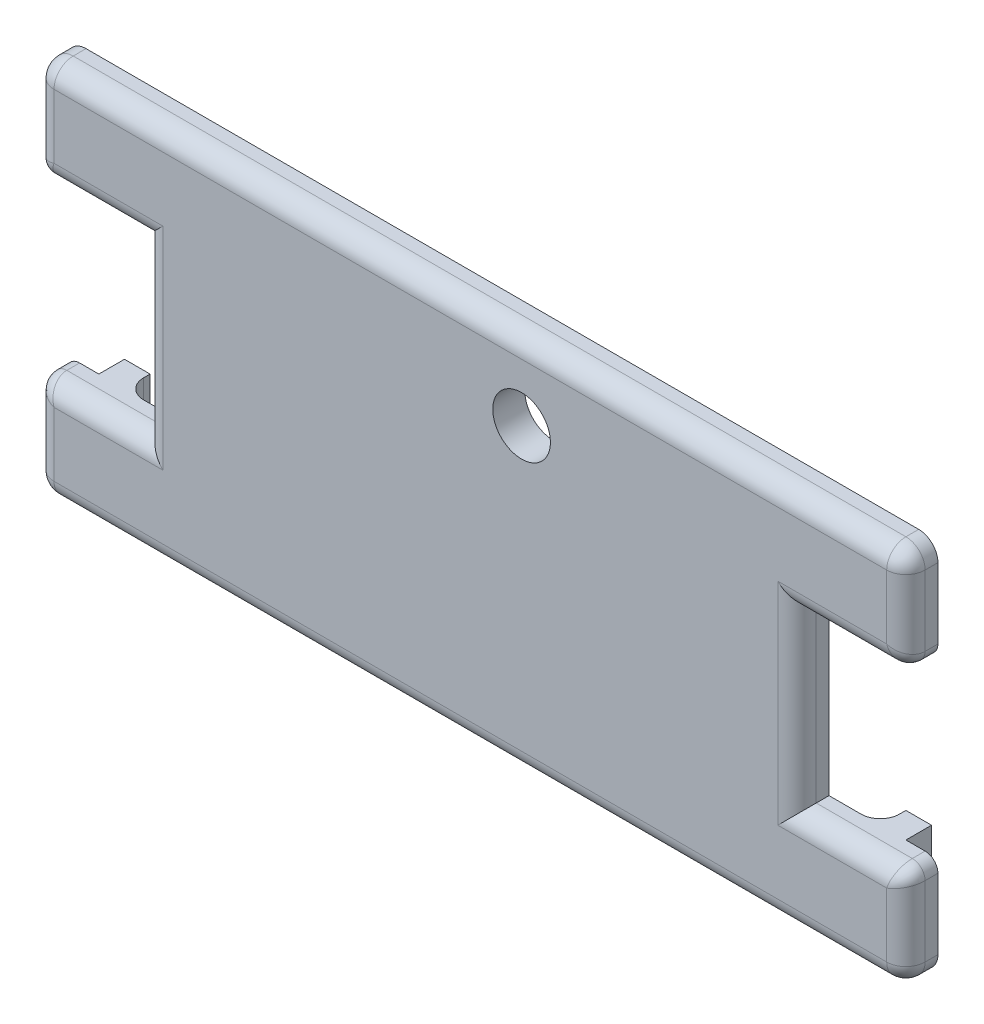
SolidWorks part; units mm, degrees
ref_plane "Front Plane" through (0, 0, 0) normal (0, 0, 1) x (1, 0, 0)
ref_plane "Top Plane" through (0, 0, 0) normal (0, 1, 0) x (1, 0, 0)
ref_plane "Right Plane" through (0, 0, 0) normal (1, 0, 0) x (0, 0, -1)
sketch "Sketch1" plane through (0, 0, 0) normal (0, 0, 1) x (1, 0, 0)
  line L16 (-34, 13.25) -> (-34, 7.75)
  line L17 (-33, 6.75) -> (-31.5, 6.75)
  line L18 (-31.5, 6.75) -> (-31.5, 10.75)
  line L19 (-30, 12.25) -> (30, 12.25)
  line L20 (31.5, 10.75) -> (31.5, 6.75)
  line L21 (31.5, 6.75) -> (33, 6.75)
  line L22 (34, 7.75) -> (34, 13.25)
  line L23 (32.5, 14.75) -> (-32.5, 14.75)
  line L24 (-34, 13.25) -> (-34, 7.75)
  line L25 (-33, 6.75) -> (-31.5, 6.75)
  line L26 (-31.5, 6.75) -> (-31.5, 10.75)
  line L27 (-30, 12.25) -> (30, 12.25)
  line L28 (31.5, 10.75) -> (31.5, 6.75)
  line L29 (31.5, 6.75) -> (33, 6.75)
  line L30 (34, 7.75) -> (34, 13.25)
  line L31 (32.5, 14.75) -> (-32.5, 14.75)
  line L40 (-31.5, -6.75) -> (-33, -6.75)
  line L41 (-34, -7.75) -> (-34, -13.25)
  line L42 (-32.5, -14.75) -> (32.5, -14.75)
  line L43 (34, -13.25) -> (34, -7.75)
  line L44 (33, -6.75) -> (31.5, -6.75)
  line L45 (31.5, -6.75) -> (31.5, -10.75)
  line L46 (30, -12.25) -> (-30, -12.25)
  line L47 (-31.5, -10.75) -> (-31.5, -6.75)
  line L48 (-31.5, -6.75) -> (-33, -6.75)
  line L49 (-34, -7.75) -> (-34, -13.25)
  line L50 (-32.5, -14.75) -> (32.5, -14.75)
  line L51 (34, -13.25) -> (34, -7.75)
  line L52 (33, -6.75) -> (31.5, -6.75)
  line L53 (31.5, -6.75) -> (31.5, -10.75)
  line L54 (30, -12.25) -> (-30, -12.25)
  line L55 (-31.5, -10.75) -> (-31.5, -6.75)
  line L64 (-36, 13.25) -> (-36, 7.75)
  line L65 (-33, 4.75) -> (-29.5, 4.75)
  line L66 (-29.5, 4.75) -> (-29.5, 10.25)
  line L67 (-29.5, 10.25) -> (29.5, 10.25)
  line L68 (29.5, 10.25) -> (29.5, 4.75)
  line L69 (29.5, 4.75) -> (33, 4.75)
  line L70 (36, 7.75) -> (36, 13.25)
  line L71 (32.5, 16.75) -> (-32.5, 16.75)
  line L72 (-36, 13.25) -> (-36, 7.75)
  line L73 (-33, 4.75) -> (-29.5, 4.75)
  line L74 (-29.5, 4.75) -> (-29.5, 10.25)
  line L75 (-29.5, 10.25) -> (29.5, 10.25)
  line L76 (29.5, 10.25) -> (29.5, 4.75)
  line L77 (29.5, 4.75) -> (33, 4.75)
  line L78 (36, 7.75) -> (36, 13.25)
  line L79 (32.5, 16.75) -> (-32.5, 16.75)
  line L80 (-31.5, 6.75) -> (-29.5, 6.75)
  line L81 (31.5, 6.75) -> (29.5, 6.75)
  line L82 (31.5, -6.75) -> (-31.5, -6.75)
  line L88 (-29.5, -4.75) -> (-33, -4.75)
  line L89 (-36, -7.75) -> (-36, -13.25)
  line L90 (-32.5, -16.75) -> (32.5, -16.75)
  line L91 (36, -13.25) -> (36, -7.75)
  line L92 (33, -4.75) -> (29.5, -4.75)
  line L93 (29.5, -4.75) -> (29.5, -10.25)
  line L94 (29.5, -10.25) -> (-29.5, -10.25)
  line L95 (-29.5, -10.25) -> (-29.5, -4.75)
  line L96 (-29.5, -4.75) -> (-33, -4.75)
  line L97 (-36, -7.75) -> (-36, -13.25)
  line L98 (-32.5, -16.75) -> (32.5, -16.75)
  line L99 (36, -13.25) -> (36, -7.75)
  line L100 (33, -4.75) -> (29.5, -4.75)
  line L101 (29.5, -4.75) -> (29.5, -10.25)
  line L102 (29.5, -10.25) -> (-29.5, -10.25)
  line L103 (-29.5, -10.25) -> (-29.5, -4.75)
  arc A12 (-34, 7.75) -> (-33, 6.75) centre (-33, 7.75) ccw
  arc A13 (-30, 12.25) -> (-31.5, 10.75) centre (-30, 10.75) ccw
  arc A14 (31.5, 10.75) -> (30, 12.25) centre (30, 10.75) ccw
  arc A15 (33, 6.75) -> (34, 7.75) centre (33, 7.75) ccw
  arc A16 (34, 13.25) -> (32.5, 14.75) centre (32.5, 13.25) ccw
  arc A17 (-32.5, 14.75) -> (-34, 13.25) centre (-32.5, 13.25) ccw
  arc A18 (-34, 7.75) -> (-33, 6.75) centre (-33, 7.75) ccw
  arc A19 (-30, 12.25) -> (-31.5, 10.75) centre (-30, 10.75) ccw
  arc A20 (31.5, 10.75) -> (30, 12.25) centre (30, 10.75) ccw
  arc A21 (33, 6.75) -> (34, 7.75) centre (33, 7.75) ccw
  arc A22 (34, 13.25) -> (32.5, 14.75) centre (32.5, 13.25) ccw
  arc A23 (-32.5, 14.75) -> (-34, 13.25) centre (-32.5, 13.25) ccw
  arc A30 (-33, -6.75) -> (-34, -7.75) centre (-33, -7.75) ccw
  arc A31 (-34, -13.25) -> (-32.5, -14.75) centre (-32.5, -13.25) ccw
  arc A32 (32.5, -14.75) -> (34, -13.25) centre (32.5, -13.25) ccw
  arc A33 (34, -7.75) -> (33, -6.75) centre (33, -7.75) ccw
  arc A34 (30, -12.25) -> (31.5, -10.75) centre (30, -10.75) ccw
  arc A35 (-31.5, -10.75) -> (-30, -12.25) centre (-30, -10.75) ccw
  arc A36 (-33, -6.75) -> (-34, -7.75) centre (-33, -7.75) ccw
  arc A37 (-34, -13.25) -> (-32.5, -14.75) centre (-32.5, -13.25) ccw
  arc A38 (32.5, -14.75) -> (34, -13.25) centre (32.5, -13.25) ccw
  arc A39 (34, -7.75) -> (33, -6.75) centre (33, -7.75) ccw
  arc A40 (30, -12.25) -> (31.5, -10.75) centre (30, -10.75) ccw
  arc A41 (-31.5, -10.75) -> (-30, -12.25) centre (-30, -10.75) ccw
  arc A48 (-36, 7.75) -> (-33, 4.75) centre (-33, 7.75) ccw
  arc A49 (33, 4.75) -> (36, 7.75) centre (33, 7.75) ccw
  arc A50 (36, 13.25) -> (32.5, 16.75) centre (32.5, 13.25) ccw
  arc A51 (-32.5, 16.75) -> (-36, 13.25) centre (-32.5, 13.25) ccw
  arc A52 (-36, 7.75) -> (-33, 4.75) centre (-33, 7.75) ccw
  arc A53 (33, 4.75) -> (36, 7.75) centre (33, 7.75) ccw
  arc A54 (36, 13.25) -> (32.5, 16.75) centre (32.5, 13.25) ccw
  arc A55 (-32.5, 16.75) -> (-36, 13.25) centre (-32.5, 13.25) ccw
  arc A62 (-33, -4.75) -> (-36, -7.75) centre (-33, -7.75) ccw
  arc A63 (-36, -13.25) -> (-32.5, -16.75) centre (-32.5, -13.25) ccw
  arc A64 (32.5, -16.75) -> (36, -13.25) centre (32.5, -13.25) ccw
  arc A65 (36, -7.75) -> (33, -4.75) centre (33, -7.75) ccw
  arc A66 (-33, -4.75) -> (-36, -7.75) centre (-33, -7.75) ccw
  arc A67 (-36, -13.25) -> (-32.5, -16.75) centre (-32.5, -13.25) ccw
  arc A68 (32.5, -16.75) -> (36, -13.25) centre (32.5, -13.25) ccw
  arc A69 (36, -7.75) -> (33, -4.75) centre (33, -7.75) ccw
  dimension "D1" = 0
  dimension "D2" = 0
  dimension "D3" = 2
  dimension "D4" = 2
extrude "Boss-Extrude1" add sketch "Sketch1" against normal blind 2 contours L28 A20 L27 A19 L26 L80 L74 L75 L76 L81 | L55 A41 L54 A40 L53 L82 L101 L102 L103 region at (0, 10.9685, 0) region at (0, -10.9685, 0)
sketch "Sketch2" plane through (0, 0, 0) normal (0, 0, 1) x (1, 0, 0)
  line L16 (-34, 13.25) -> (-34, 7.75)
  line L17 (-33, 6.75) -> (-31.5, 6.75)
  line L18 (-31.5, 6.75) -> (-31.5, 10.75)
  line L19 (-30, 12.25) -> (30, 12.25)
  line L20 (31.5, 10.75) -> (31.5, 6.75)
  line L21 (31.5, 6.75) -> (33, 6.75)
  line L22 (34, 7.75) -> (34, 13.25)
  line L23 (32.5, 14.75) -> (-32.5, 14.75)
  line L24 (-34, 13.25) -> (-34, 7.75)
  line L25 (-33, 6.75) -> (-31.5, 6.75)
  line L26 (-31.5, 6.75) -> (-31.5, 10.75)
  line L27 (-30, 12.25) -> (30, 12.25)
  line L28 (31.5, 10.75) -> (31.5, 6.75)
  line L29 (31.5, 6.75) -> (33, 6.75)
  line L30 (34, 7.75) -> (34, 13.25)
  line L31 (32.5, 14.75) -> (-32.5, 14.75)
  line L32 (-31.5, -6.75) -> (-31.5, 6.75)
  line L33 (31.5, 6.75) -> (29.5, 6.75)
  line L34 (29.5, 6.75) -> (25.5, 6.75)
  line L35 (25.5, 6.75) -> (25.5, -6.75)
  line L36 (25.5, -6.75) -> (29.5, -6.75)
  line L37 (-29.5, -6.75) -> (-25.5, -6.75)
  line L38 (-25.5, -6.75) -> (-25.5, 6.75)
  line L39 (-25.5, 6.75) -> (-29.5, 6.75)
  line L40 (-31.5, -6.75) -> (-33, -6.75)
  line L41 (-34, -7.75) -> (-34, -13.25)
  line L42 (-32.5, -14.75) -> (32.5, -14.75)
  line L43 (34, -13.25) -> (34, -7.75)
  line L44 (33, -6.75) -> (31.5, -6.75)
  line L45 (31.5, -6.75) -> (31.5, -10.75)
  line L46 (30, -12.25) -> (-30, -12.25)
  line L47 (-31.5, -10.75) -> (-31.5, -6.75)
  line L48 (-31.5, -6.75) -> (-33, -6.75)
  line L49 (-34, -7.75) -> (-34, -13.25)
  line L50 (-32.5, -14.75) -> (32.5, -14.75)
  line L51 (34, -13.25) -> (34, -7.75)
  line L52 (33, -6.75) -> (31.5, -6.75)
  line L53 (31.5, -6.75) -> (31.5, -10.75)
  line L54 (30, -12.25) -> (-30, -12.25)
  line L55 (-31.5, -10.75) -> (-31.5, -6.75)
  line L56 (-29.5, 6.75) -> (-31.5, 6.75)
  line L57 (-29.5, -6.75) -> (-31.5, -6.75)
  line L58 (29.5, -6.75) -> (31.5, -6.75)
  line L59 (31.5, 6.75) -> (29.5, 6.75)
  arc A12 (-34, 7.75) -> (-33, 6.75) centre (-33, 7.75) ccw
  arc A13 (-30, 12.25) -> (-31.5, 10.75) centre (-30, 10.75) ccw
  arc A14 (31.5, 10.75) -> (30, 12.25) centre (30, 10.75) ccw
  arc A15 (33, 6.75) -> (34, 7.75) centre (33, 7.75) ccw
  arc A16 (34, 13.25) -> (32.5, 14.75) centre (32.5, 13.25) ccw
  arc A17 (-32.5, 14.75) -> (-34, 13.25) centre (-32.5, 13.25) ccw
  arc A18 (-34, 7.75) -> (-33, 6.75) centre (-33, 7.75) ccw
  arc A19 (-30, 12.25) -> (-31.5, 10.75) centre (-30, 10.75) ccw
  arc A20 (31.5, 10.75) -> (30, 12.25) centre (30, 10.75) ccw
  arc A21 (33, 6.75) -> (34, 7.75) centre (33, 7.75) ccw
  arc A22 (34, 13.25) -> (32.5, 14.75) centre (32.5, 13.25) ccw
  arc A23 (-32.5, 14.75) -> (-34, 13.25) centre (-32.5, 13.25) ccw
  arc A30 (-33, -6.75) -> (-34, -7.75) centre (-33, -7.75) ccw
  arc A31 (-34, -13.25) -> (-32.5, -14.75) centre (-32.5, -13.25) ccw
  arc A32 (32.5, -14.75) -> (34, -13.25) centre (32.5, -13.25) ccw
  arc A33 (34, -7.75) -> (33, -6.75) centre (33, -7.75) ccw
  arc A34 (30, -12.25) -> (31.5, -10.75) centre (30, -10.75) ccw
  arc A35 (-31.5, -10.75) -> (-30, -12.25) centre (-30, -10.75) ccw
  arc A36 (-33, -6.75) -> (-34, -7.75) centre (-33, -7.75) ccw
  arc A37 (-34, -13.25) -> (-32.5, -14.75) centre (-32.5, -13.25) ccw
  arc A38 (32.5, -14.75) -> (34, -13.25) centre (32.5, -13.25) ccw
  arc A39 (34, -7.75) -> (33, -6.75) centre (33, -7.75) ccw
  arc A40 (30, -12.25) -> (31.5, -10.75) centre (30, -10.75) ccw
  arc A41 (-31.5, -10.75) -> (-30, -12.25) centre (-30, -10.75) ccw
  line M31 (-34, 13.25) -> (-34, 7.75)
  arc M32 (-34, 7.75) -> (-33, 6.75) centre (-33, 7.75) ccw
  line M33 (-33, 6.75) -> (-31.5, 6.75)
  line M34 (-31.5, 6.75) -> (-31.5, 10.75)
  arc M35 (-31.5, 10.75) -> (-30, 12.25) centre (-30, 10.75) cw
  line M36 (-30, 12.25) -> (30, 12.25)
  arc M37 (30, 12.25) -> (31.5, 10.75) centre (30, 10.75) cw
  line M38 (31.5, 10.75) -> (31.5, 6.75)
  line M39 (31.5, 6.75) -> (33, 6.75)
  arc M40 (33, 6.75) -> (34, 7.75) centre (33, 7.75) ccw
  line M41 (34, 7.75) -> (34, 13.25)
  arc M42 (34, 13.25) -> (32.5, 14.75) centre (32.5, 13.25) ccw
  line M43 (32.5, 14.75) -> (-32.5, 14.75)
  arc M44 (-32.5, 14.75) -> (-34, 13.25) centre (-32.5, 13.25) ccw
  dimension "D3" = 4
  dimension "D4" = 4
  dimension "D1" = 0
  dimension "D2" = 0
extrude "Boss-Extrude2" add sketch "Sketch2" along normal blind 2.5 contours L55 A41 L54 A40 L53 L58 L36 L35 L34 L33 L56 L39 L38 L37 L57 M38 M37 M36 M35 M34 | M44 M31 M32 M33 M34 M35 M36 M37 M38 M39 M40 M41 M42 M43 | A41 L55 L48 A36 L49 A37 L50 A38 L51 A39 L52 L53 A40 L54 region at (0, 12.9438, 0) region at (0, 0, 0) region at (0, -12.9438, 0)
fillet "Fillet1" radius 1.5 26 edges at (-25.5, 0, 2.5) (-29.25, 6.75, 2.5) (-33.7071, 7.0429, 2.5) (-34, 10.5, 2.5) (-33.5607, 14.3107, 2.5) (0, 14.75, 2.5) (33.5607, 14.3107, 2.5) (34, 10.5, 2.5) (33.7071, 7.0429, 2.5) (29.25, 6.75, 2.5) (25.5, 0, 2.5) (29.25, -6.75, 2.5) (33.7071, -7.0429, 2.5) (34, -10.5, 2.5) (33.5607, -14.3107, 2.5) (0, -14.75, 2.5) (-33.5607, -14.3107, 2.5) (-34, -10.5, 2.5) (-33.7071, -7.0429, 2.5) (-29.25, -6.75, 2.5) (-29.5, -8.5, 0) (0, -10.25, 0) (29.5, -8.5, 0) (29.5, 8.5, 0) (-29.5, 8.5, 0) (0, 10.25, 0)
sketch "Sketch3" plane through (0, 0, 2.5) normal (0, 0, 1) x (1, 0, 0)
  line L0 (24, 8.75) -> (4, 8.75)
  line L1 (24, -8.25) -> (24, 8.25) construction
  line L2 (4, 8.75) -> (4, 16.2657)
  line L3 (4, 16.2657) -> (4, 13.25)
  line L4 (32.5, 13.25) -> (-32.5, 13.25) construction
  line L5 (-32.5, 14.75) -> (32.5, 14.75) construction
  line L6 (34, 13.25) -> (34, 7.75) construction
  circle A0 centre (4, 8.75) radius 2.25
  dimension "D1" = 6
  dimension "D2" = 30
extrude "Cut-Extrude1" cut sketch "Sketch3" against normal blind 10 contours L2 A0 L0 | L0 A0 L2 region at (3.6817, 8.4317, 2.5) region at (4.9549, 9.7049, 2.5)
